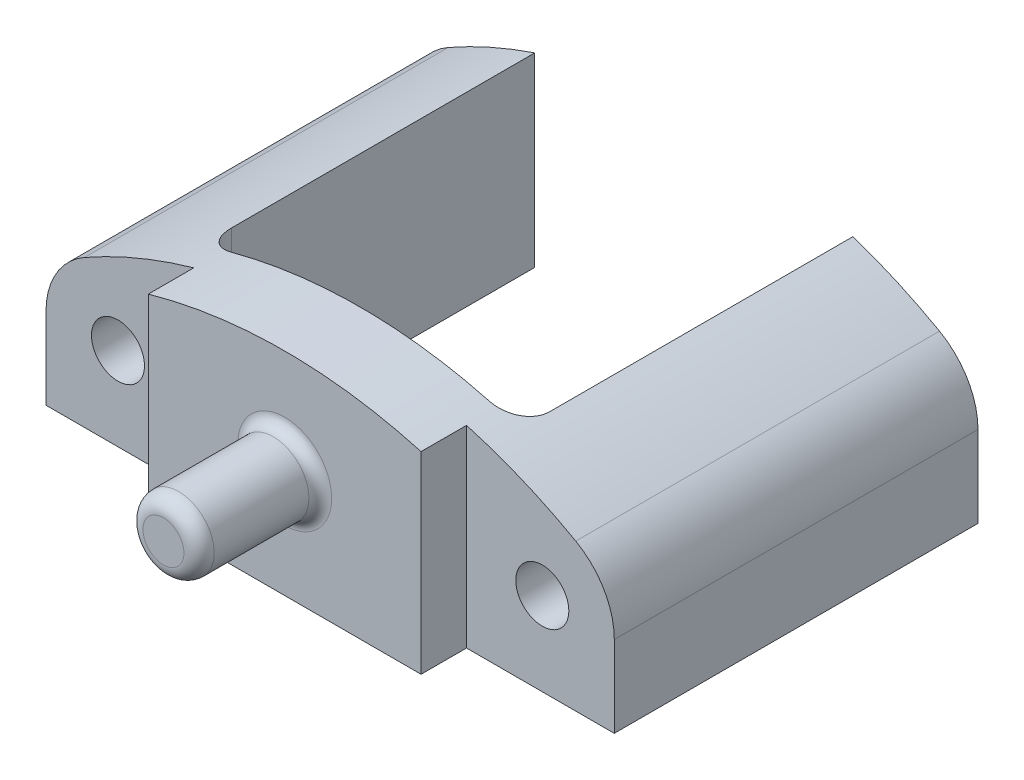
SolidWorks part; units mm, degrees
ref_plane "Front Plane" through (0, 0, 0) normal (0, 0, 1) x (1, 0, 0)
ref_plane "Top Plane" through (0, 0, 0) normal (0, 1, 0) x (1, 0, 0)
ref_plane "Right Plane" through (0, 0, 0) normal (1, 0, 0) x (0, 0, -1)
sketch "Sketch1" plane through (0, 0, 0) normal (0, 0, 1) x (1, 0, 0)
  line L1 (-23.8125, 36.7793) -> (-23.8125, 24.0793)
  line L2 (23.8125, 36.7793) -> (23.8125, 24.0793)
  line L3 (23.8125, 24.0793) -> (-23.8125, 24.0793)
  line L4 (0, 48.4053) -> (0, 0)
  arc A0 (23.8125, 36.7793) -> (-23.8125, 36.7793) centre (0, 0) ccw
  circle A1 centre (17.78, 31.0643) radius 2.2225
  circle A2 centre (-17.78, 31.0643) radius 2.2225
  dimension "D1" = 87.63
  dimension "D4" = 4.445
  dimension "D2" = 47.625
  dimension "D3" = 12.7
  dimension "D5" = 17.78
  dimension "D6" = 6.985
extrude "Boss-Extrude1" add sketch "Sketch1" along normal blind 6.35 contours L4 A0 L1 L3 A2 | L2 A0 L4 L3 A1 region at (-10.8638, 33.0102, 0) region at (10.8638, 33.0102, 0)
sketch "Sketch2" plane through (0, 0, 6.35) normal (0, 0, 1) x (1, 0, 0)
  line L0 (23.8125, 24.0793) -> (-23.8125, 24.0793) construction
  circle A0 centre (0, 33.0963) radius 2.9845
  dimension "D1" = 5.969
  dimension "D2" = 9.017
extrude "Boss-Extrude2" add sketch "Sketch2" along normal blind 10.16
fillet "Fillet1" radius 1.27 1 edges at (2.9845, 33.0963, 16.51)
fillet "Fillet2" radius 0.9525 1 edges at (2.9845, 33.0963, 6.35)
sketch "Sketch3" plane through (0, 0, 0) normal (0, 0, -1) x (-1, 0, 0)
  circle A0 centre (0, 33.1354) radius 6.35
extrude "Cut-Extrude1" cut sketch "Sketch3" against normal blind 4.445
fillet "Fillet3" radius 1.27 2 edges at (-6.35, 33.1354, 0) (-6.35, 33.1354, 4.445)
sketch "Sketch4" plane through (0, 0, 6.35) normal (0, 0, 1) x (1, 0, 0)
  line L2 (-11.43, 43.0021) -> (-28.3375, 46.1756)
  line L3 (-28.3375, 46.1756) -> (-28.8895, 24.7143)
  line L4 (-28.8895, 24.7143) -> (-14.7121, 19.1661)
  line L5 (-14.7121, 19.1661) -> (-11.43, 21.9402)
  line L7 (0, -9.0805) -> (0, 9.0805) construction
  line L8 (28.8895, 24.7143) -> (14.7121, 19.1661)
  line L9 (14.7121, 19.1661) -> (11.43, 21.9402)
  line L10 (11.43, 31.0643) -> (11.43, 21.9402)
  line L11 (11.43, 31.0643) -> (11.43, 43.0021)
  line L12 (28.3375, 46.1756) -> (28.8895, 24.7143)
  line L13 (11.43, 43.0021) -> (28.3375, 46.1756)
  line L14 (-11.43, 43.0021) -> (-11.43, 21.9402)
extrude "Cut-Extrude3" cut sketch "Sketch4" against normal blind 3.81
sketch "Sketch5" plane through (0, 0, 0) normal (0, 0, -1) x (-1, 0, 0)
  line L7 (-13.335, 41.7365) -> (-13.335, 24.0793)
  line L8 (23.8125, 36.7793) -> (23.8125, 24.0793)
  line L9 (23.8125, 24.0793) -> (23.8125, 36.7793)
  line L10 (-23.8125, 24.0793) -> (23.8125, 24.0793)
  line L11 (-23.8125, 36.7793) -> (-23.8125, 24.0793)
  line L13 (-23.8125, 24.0793) -> (-13.335, 24.0793)
  line L14 (-23.8125, 36.7793) -> (-23.8125, 24.0793)
  line L15 (13.335, 41.7365) -> (13.335, 24.0793)
  line L16 (23.8125, 24.0793) -> (13.335, 24.0793)
  arc A5 (23.8125, 36.7793) -> (-23.8125, 36.7793) centre (0, 0) ccw
  circle A8 centre (-17.78, 31.0643) radius 2.2225
  circle A9 centre (-17.78, 31.0643) radius 2.2225
  arc A10 (-13.335, 41.7365) -> (-23.8125, 36.7793) centre (0, 0) ccw
  circle A11 centre (17.78, 31.0643) radius 2.2225
  circle A12 centre (17.78, 31.0643) radius 2.2225
  arc A13 (13.335, 41.7365) -> (23.8125, 36.7793) centre (0, 0) cw
  dimension "D1" = 0
  dimension "D2" = 0
  dimension "D3" = 0
extrude "Boss-Extrude3" add sketch "Sketch5" along normal blind 27.94
fillet "Fillet4" radius 2.54 2 edges at (-13.335, 32.9079, 0) (13.335, 32.9079, 0)
sketch "Sketch6" plane through (0, 0, -27.94) normal (0, 0, -1) x (-1, 0, 0)
  circle A0 centre (0, 0) radius 41.8353
  circle A1 centre (0, 0) radius 48.0082
extrude "Cut-Extrude4" cut sketch "Sketch6" against normal through all both and the other way through all
fillet "Fillet5" radius 6.35 2 edges at (23.8125, 34.3971, -12.7) (-23.8125, 34.3971, -12.7)
